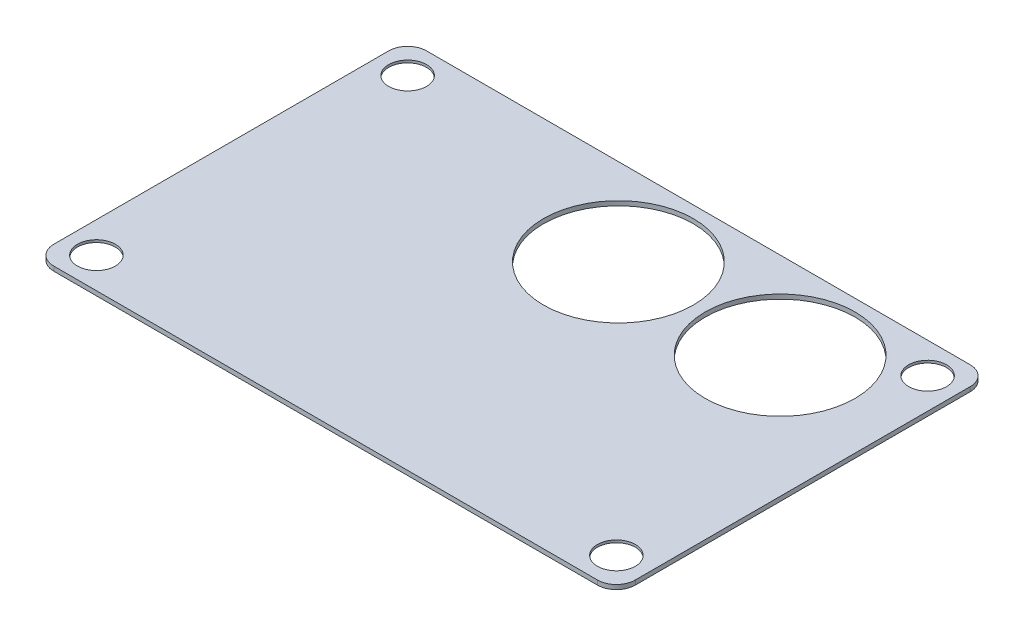
SolidWorks part; units mm, degrees
ref_plane "Front Plane" through (0, 0, 0) normal (0, 0, 1) x (1, 0, 0)
ref_plane "Top Plane" through (0, 0, 0) normal (0, 1, 0) x (1, 0, 0)
ref_plane "Right Plane" through (0, 0, 0) normal (1, 0, 0) x (0, 0, -1)
sketch "Sketch1" plane through (0, 0, 0) normal (0, 1, 0) x (1, 0, 0)
  line L1 (0, 0) -> (78, 0)
  line L2 (0, 0) -> (0, 50)
  line L3 (0, 50) -> (78, 50)
  line L4 (78, 0) -> (78, 50)
  dimension "D1" = 78
  dimension "D2" = 50
extrude "pcb" add sketch "Sketch1" along normal blind 0.6
fillet "card edges" radius 2.54 4 edges at (78, 0.3, -50) (0, 0.3, -50) (0, 0.3, 0) (78, 0.3, 0)
sketch "Sketch4" plane through (0, 0.6, 0) normal (0, 1, 0) x (1, 0, 0)
  line L11 (0, 47.46) -> (0, 2.54) construction
  line L13 (2.54, 0) -> (75.46, 0) construction
  circle A0 centre (4.1275, 4.13) radius 2.54
  dimension "D1" = 5.08
  dimension "D2" = 1.5875
  dimension "D3" = 1.59
extrude "magnet hole cut" cut sketch "Sketch4" against normal through all
sketch "Sketch8" plane through (0, 0, 0) normal (0, -1, 0) x (1, 0, 0)
  circle A0 centre (4.1275, -4.13) radius 3.33
  circle A1 centre (4.1275, -4.13) radius 2.54 construction
  dimension "D1" = 0.79
extrude "steel inlay cut" cut sketch "Sketch8" against normal blind 0.2666
ref_plane "Plane1" through (39, 0, 0) normal (1, 0, 0) x (0, 0, -1)
ref_plane "Plane2" through (0, 0, -25) normal (0, 0, 1) x (1, 0, 0)
mirror "Mirror1" about plane through (0, 0, -25) normal (0, 0, 1) of "steel inlay cut", "magnet hole cut"
mirror "Mirror2" about plane through (39, 0, 0) normal (1, 0, 0) of "Mirror1"
sketch "Sketch15" plane through (0, 0.6, 0) normal (0, 1, 0) x (1, 0, 0)
  line L3 (75.46, 50) -> (2.54, 50) construction
  line L4 (78, 2.54) -> (78, 47.46) construction
  circle A0 centre (61.6, 38.3625) radius 10.05
  circle A1 centre (39.9125, 38.3625) radius 10.05
  dimension "D2" = 1.5875
  dimension "D1" = 20.1
  dimension "D4" = 1.5875
  dimension "D3" = 6.35
extrude "battery_holes" cut sketch "Sketch15" against normal through all
equation "\"magnet_inset\"= 0.0625in"
equation "\"magnet_diameter\" = 0.2in"
equation "\"D1@Sketch4\"=\"magnet_diameter\""
equation "\"steel_inset_distance\" = 1in / 32"
equation "\"D1@steel inlay cut\"= \"pcb_thickness\" - ( ( \"magnet_thickness\" / 2 ) - ( \"kapton_thickness\" / 2 ) )"
equation "\"kapton_thickness\"= 0.005in"
equation "\"pcb_thickness\"= 0.6mm"
equation "\"magnet_thickness\" = 0.03125in"
equation "\"D2@Sketch4\"=\"magnet_inset\""
equation "\"edge_radius\" = 1in / 10"
equation "\"card_width\" = 78mm"
equation "\"card_height\" = 50mm"
equation "\"battery_diameter\" = 20mm"
equation "\"battery_oversize\" = 0.1mm"
equation "\"battery_vertical_inset\" = 1in / 16"
equation "\"battery_horizontal_inset\" = 1in / 4"
equation "\"battery_spacing\" = 1in / 16"
equation "\"D1@Sketch15\"=\"battery_diameter\"+\"battery_oversize\""
equation "\"D4@Sketch15\"=\"battery_spacing\""
equation "\"D2@Sketch15\"=\"battery_vertical_inset\""
equation "\"D3@Sketch15\"=\"battery_horizontal_inset\""
equation "\"D2@Sketch1\"=\"card_height\""
equation "\"D1@Sketch1\"=\"card_width\""
equation "\"D1@Plane1\"=\"card_width\"/2"
equation "\"D1@Plane2\"=\"card_height\"/2"
